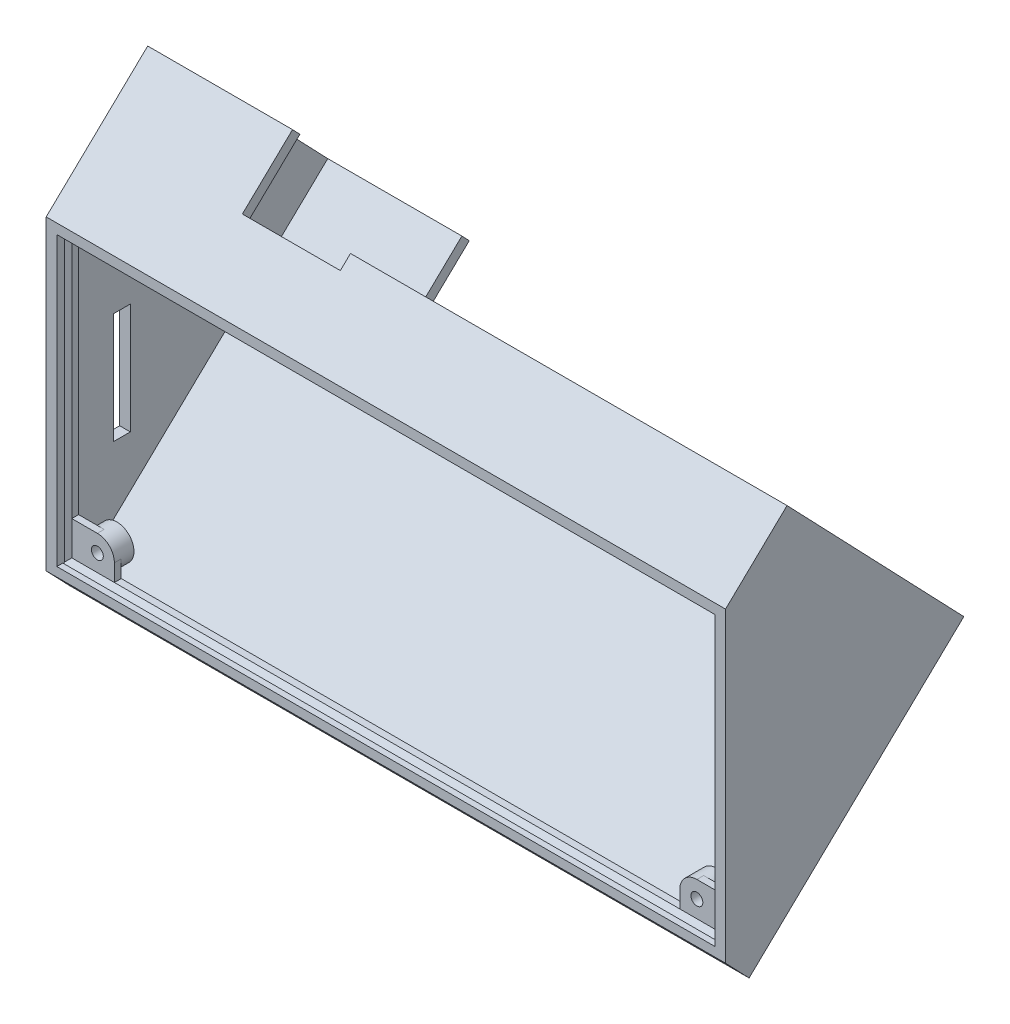
SolidWorks part; units mm, degrees
material "ABS"
ref_plane "Front Plane" through (0, 0, 0) normal (0, 0, 1) x (1, 0, 0)
ref_plane "Top Plane" through (0, 0, 0) normal (0, 1, 0) x (1, 0, 0)
ref_plane "Right Plane" through (0, 0, 0) normal (1, 0, 0) x (0, 0, -1)
sketch "Sketch1" plane through (0, 0, 0) normal (0, 0, 1) x (1, 0, 0)
  line L0 (-81.1699, 37.1521) -> (78.3301, 37.1521)
  line L1 (-78.6699, -32.8479) -> (75.8301, -32.8479)
  line L2 (-78.6699, -32.8479) -> (-78.6699, 34.6521)
  line L3 (-78.6699, 34.6521) -> (75.8301, 34.6521)
  line L4 (75.8301, -32.8479) -> (75.8301, 34.6521)
  line L5 (-78.6699, -32.8479) -> (75.8301, 34.6521) construction
  line L6 (-78.6699, 34.6521) -> (75.8301, -32.8479) construction
  line L7 (78.3301, -35.3479) -> (78.3301, 37.1521)
  line L8 (-81.1699, -35.3479) -> (78.3301, -35.3479)
  line L9 (-81.1699, -35.3479) -> (-81.1699, 37.1521)
  line L10 (-78.4199, 34.4021) -> (75.5801, 34.4021) construction
  line L11 (-78.4199, -32.5979) -> (-78.4199, 34.4021) construction
  line L13 (75.5801, 34.4021) -> (75.5801, -32.5979) construction
  line L14 (75.5801, -32.5979) -> (-78.4199, -32.5979) construction
  point P0 (0, 0)
  dimension "D2" = 0.25
  dimension "D3" = 0.25
  dimension "D4" = 0.25
  dimension "D5" = 0.25
  dimension "D1" = 2.5
ref_plane "Plane1" through (-81.1699, 0, 0) normal (1, 0, 0) x (0, 1, 0)
sketch "Sketch3" plane through (-81.1699, 0, 0) normal (1, 0, 0) x (0, 1, 0)
  line L0 (37, 0) -> (50.8332, -14.4444)
  line L1 (-35.3479, 0) -> (37.1521, 0) construction
  line L2 (-35.3479, 0) -> (37.1521, 0) construction
  line L3 (50.8332, -14.4444) -> (7.4999, -55.9441)
  line L4 (-35, 0) -> (-40.7778, -5.5333)
  line L5 (-40.7778, -5.5333) -> (7.4999, -55.9441)
  line L6 (37, 0) -> (-35, 0)
  dimension "D1" = 72
  dimension "D2" = 20
  dimension "D3" = 8
  dimension "D4" = 60
  dimension "D5" = 35
extrude "Boss-Extrude3" add sketch "Sketch3" along normal up to vertex (159.5 mm away) up to point (78.3301, 37.1521, 0)
shell "Shell1" thickness 2.5 removed face at (-1.4199, 1, 0)
extrude "Cut-Extrude2" cut sketch "Sketch1" against normal blind 4 contours L3 L4 L1 L2
sketch "Sketch2" plane through (-81.1699, 0, 0) normal (-1, 0, 0) x (0, 0, 1)
  line L1 (-17.25, -14.0979) -> (-13.25, -14.0979)
  line L2 (-17.25, -14.0979) -> (-17.25, 11.9021)
  line L3 (-17.25, 11.9021) -> (-13.25, 11.9021)
  line L4 (-13.25, -14.0979) -> (-13.25, 11.9021)
  line L5 (-17.25, -14.0979) -> (-13.25, 11.9021) construction
  line L6 (-17.25, 11.9021) -> (-13.25, -14.0979) construction
  point P0 (-15.25, -1.0979)
  dimension "D1" = 1.0979
  dimension "D2" = 4
  dimension "D3" = 26
  dimension "D4" = 15.25
extrude "Cut-Extrude1" cut sketch "Sketch2" against normal up to next
ref_plane "Plane2" through (0, 0, -1.8) normal (0, 0, 1) x (1, 0, 0)
sketch "Sketch6" plane through (0, 0, -1.8) normal (0, 0, 1) x (1, 0, 0)
  line L0 (-78.6699, 34.6521) -> (75.8301, 34.6521) construction
  line L1 (-78.6699, 34.6521) -> (-78.6699, -32.8479) construction
  line L2 (-78.6699, -32.8479) -> (75.8301, -32.8479) construction
  line L3 (75.8301, 34.6521) -> (75.8301, -32.8479) construction
  line L4 (-78.6699, 34.6521) -> (75.8301, 34.6521)
  line L5 (-78.6699, 34.6521) -> (-78.6699, -32.8479)
  line L6 (-78.6699, -32.8479) -> (75.8301, -32.8479)
  line L7 (75.8301, 34.6521) -> (75.8301, -32.8479)
sketch "Sketch7" plane through (75.8301, 0, 0) normal (-1, 0, 0) x (0, 0, 1)
  line L0 (-1.3568, 35.1148) -> (-2.6364, 33.7787)
  line L1 (-2.6364, 33.7787) -> (-4.2364, 33.7787)
  line L2 (-4.2364, 33.7787) -> (-4.2364, 37.8725)
  line L3 (-4.2364, 37.8725) -> (-1.3568, 35.1148)
  line L4 (-14.368, 47.2985) -> (-1.1628, 34.6521) construction
  dimension "D1" = 90
  dimension "D2" = 0.2
  dimension "D3" = 1.65
  dimension "D4" = 1.6
sweep "Sweep1" add profiles "Sketch7" path "Sketch6"
sketch "Sketch8" plane through (0, 0, 0) normal (0, 0, 1) x (1, 0, 0)
  line L0 (-91.1699, 60.8332) -> (88.3301, 60.8332)
  line L1 (-81.1699, 50.8332) -> (78.3301, 50.8332)
  line L2 (-81.1699, 50.8332) -> (-81.1699, -40.7778)
  line L3 (-81.1699, -40.7778) -> (78.3301, -40.7778)
  line L4 (78.3301, 50.8332) -> (78.3301, -40.7778)
  line L5 (88.3301, 60.8332) -> (88.3301, -50.7778)
  line L6 (-91.1699, -50.7778) -> (88.3301, -50.7778)
  line L7 (-91.1699, 60.8332) -> (-91.1699, -50.7778)
  dimension "D1" = 10
extrude "Cut-Extrude3" cut sketch "Sketch8" against normal through all
sketch "Sketch10" plane through (0, 31.5338, -32.9272) normal (0, 0.6917, -0.7222) x (-1, 0, 0)
  line L0 (78.6699, -30.7778) -> (78.6699, 24.2222)
  line L1 (81.1699, -33.2778) -> (47.1699, -33.2778)
  line L2 (81.1699, -33.2778) -> (81.1699, 26.7222)
  line L3 (81.1699, 26.7222) -> (47.1699, 26.7222)
  line L4 (47.1699, -33.2778) -> (47.1699, -30.7778)
  line L5 (78.6699, 24.2222) -> (47.1699, 24.2222)
  line L6 (78.6699, -30.7778) -> (78.6699, 24.2222) construction
  line L7 (78.6699, -30.7778) -> (47.1699, -30.7778)
  line L8 (49.6699, -30.7778) -> (49.6699, 24.2222) construction
  line L9 (78.6699, 24.2222) -> (49.6699, 24.2222) construction
  line L10 (78.6699, -30.7778) -> (49.6699, -30.7778) construction
  line L11 (47.1699, 24.2222) -> (47.1699, 26.7222)
  line L12 (47.1699, -33.2778) -> (47.1699, 26.7222) construction
  line L13 (47.1699, 24.2222) -> (47.1699, -30.7778)
  line M1 (81.1699, -33.2778) -> (81.1699, 26.7222)
  line M2 (81.1699, 26.7222) -> (-78.3301, 26.7222)
  line M4 (-78.3301, -33.2778) -> (81.1699, -33.2778)
  dimension "D1" = 34
extrude "Cut-Extrude4" cut sketch "Sketch10" against normal up to surface (2.5 mm away) contours L5 L13 L7 L0 region at (-62.9199, 29.1666, -35.1943) up to face at (-1.4199, 27.4374, -33.3887)
extrude "Boss-Extrude4" add sketch "Sketch10<3>" along normal blind 13 contours L11 L5 L0 L7 L4 M4 M1 M2 region at (-79.3596, 29.1666, -35.1943)
sketch "Sketch10<3>" plane through (0, 31.5338, -32.9272) normal (0, 0.6917, -0.7222) x (-1, 0, 0) same geometry as "Sketch10"
sketch "Sketch12" plane through (0, 31.5338, -32.9272) normal (0, 0.6917, -0.7222) x (-1, 0, 0)
  line L0 (47.1699, -33.2778) -> (-15.8301, -33.2778)
  line L1 (-78.3301, -33.2778) -> (47.1699, -33.2778) construction
  line L2 (-15.8301, -33.2778) -> (-15.8301, -13.2778)
  line L3 (-15.8301, -13.2778) -> (24.1699, 26.7222)
  line L4 (-78.3301, 26.7222) -> (47.1699, 26.7222) construction
  line L5 (24.1699, 26.7222) -> (47.1699, 26.7222)
  line L6 (47.1699, 26.7222) -> (47.1699, -33.2778)
  dimension "D1" = 63
  dimension "D2" = 135
  dimension "D3" = 20
extrude "Cut-Extrude5" cut sketch "Sketch12" against normal blind 3.302
sketch "Sketch13" plane through (0, 31.5338, -32.9272) normal (0, 0.6917, -0.7222) x (-1, 0, 0)
  line L0 (-78.3301, -23.2778) -> (-15.8301, -23.2778) construction
  line L1 (-78.3301, -33.2778) -> (-78.3301, 26.7222) construction
  line L2 (-78.3301, -33.2778) -> (-15.8301, -33.2778) construction
  line L4 (-15.8301, -13.2778) -> (-15.8301, -33.2778) construction
  circle A0 centre (-68.3301, -23.2778) radius 2.6
  circle A1 centre (-33.3301, -23.2778) radius 2.6
  circle A2 centre (1.6699, -23.2778) radius 2.6 [skipped]
  circle A3 centre (-33.3301, 16.7222) radius 2.6
  circle A4 centre (1.6699, 16.7222) radius 2.6
  circle A5 centre (-68.3301, 16.7222) radius 2.6
  dimension "D1" = 5.2
  dimension "D2" = 10
  dimension "D6" = 40
  dimension "D7" = 35
  dimension "D3" = 10
  dimension "D4" = 3
  dimension "D5" = 2
extrude "Cut-Extrude6" cut sketch "Sketch13" against normal up to surface (2.5 mm away) up to face at (32.3301, 25.993, -34.772)
sketch "Sketch14" plane through (0, 0, -4.2364) normal (0, 0, -1) x (-1, 0, 0)
  line L0 (1.4199, -31.9746) -> (1.4199, -9.1254) construction
  line L1 (77.7966, -31.9746) -> (67.7966, -31.9746)
  line L2 (77.7966, -31.9746) -> (77.7966, -23.9746)
  line L3 (77.7966, -23.9746) -> (71.7966, -23.9746)
  line L4 (67.7966, -31.9746) -> (67.7966, -27.9746)
  line L5 (77.7966, -31.9746) -> (-74.9567, -31.9746) construction
  line L6 (-74.9567, -31.9746) -> (-64.9567, -31.9746)
  line L7 (-64.9567, -31.9746) -> (-64.9567, -27.9746)
  line L8 (-74.9567, -23.9746) -> (-68.9567, -23.9746)
  line L9 (-74.9567, -31.9746) -> (-74.9567, -23.9746)
  arc A0 (71.7966, -23.9746) -> (67.7966, -27.9746) centre (71.7966, -27.9746) ccw
  arc A1 (-68.9567, -23.9746) -> (-64.9567, -27.9746) centre (-68.9567, -27.9746) cw
  point P7 (67.7966, -23.9746)
  point P12 (1.4199, -31.9746)
  dimension "D3" = 4
  dimension "D1" = 8
  dimension "D2" = 10
extrude "Boss-Extrude5" add sketch "Sketch14" against normal up to vertex (1.6 mm away) up to point (-77.7966, -31.9746, -2.6364)
sketch "Sketch15" plane through (0, 0, -4.2364) normal (0, 0, -1) x (-1, 0, 0)
  circle A0 centre (71.7966, -27.9746) radius 4
  circle A1 centre (71.7966, -27.9746) radius 1.4
  arc A2 (71.7966, -23.9746) -> (67.7966, -27.9746) centre (71.7966, -27.9746) ccw construction
  circle A3 centre (-68.9567, -27.9746) radius 4
  circle A4 centre (-68.9567, -27.9746) radius 1.4
  arc A5 (-64.9567, -27.9746) -> (-68.9567, -23.9746) centre (-68.9567, -27.9746) ccw construction
  dimension "D1" = 2.8
extrude "Boss-Extrude6" add sketch "Sketch15" along normal blind 3
extrude "Cut-Extrude7" cut sketch "Sketch15<2>" against normal up to next contours A4 | A1
sketch "Sketch15<2>" plane through (0, 0, -4.2364) normal (0, 0, -1) x (-1, 0, 0) same geometry as "Sketch15"
sketch "Sketch16" plane through (0, 0, 0) normal (0, 0, 1) x (1, 0, 0)
  line L0 (78.3301, 37) -> (-81.1699, 37) construction
  line L1 (78.3301, -35) -> (-81.1699, -35) construction
  line L2 (70.8301, -35) -> (78.3301, -35)
  line L3 (78.3301, 29.5) -> (78.3301, 37)
  line L4 (6.0801, 37) -> (-8.9199, 37)
  line L5 (-73.6699, 37) -> (-81.1699, 37)
  line L6 (-81.1699, 37) -> (-81.1699, -35)
  line L7 (-81.1699, -35) -> (78.3301, -35)
  line L8 (78.3301, -35) -> (78.3301, 37)
  line L9 (78.3301, 37) -> (-81.1699, 37)
  line L10 (-81.1699, 37) -> (-81.1699, 29.5)
  line L11 (-81.1699, -35) -> (-73.6699, -35)
  line L12 (78.3301, -35) -> (78.3301, -27.5)
  line L13 (78.3301, 37) -> (70.8301, 37)
  line L14 (-81.1699, -27.5) -> (-81.1699, -35)
  line L15 (-8.9199, -35) -> (6.0801, -35)
  arc A0 (-73.6699, 37) -> (-81.1699, 29.5) centre (-81.1699, 37) ccw
  arc A1 (78.3301, 29.5) -> (70.8301, 37) centre (78.3301, 37) ccw
  arc A2 (70.8301, -35) -> (78.3301, -27.5) centre (78.3301, -35) ccw
  arc A3 (-81.1699, -27.5) -> (-73.6699, -35) centre (-81.1699, -35) ccw
  arc A4 (6.0801, 37) -> (-8.9199, 37) centre (-1.4199, 37) ccw
  arc A5 (-8.9199, -35) -> (6.0801, -35) centre (-1.4199, -35) ccw
  dimension "D1" = 15
  dimension "D2" = 0
extrude "Pads For Printing" [suppressed] add sketch "Sketch16" against normal blind 0.3
